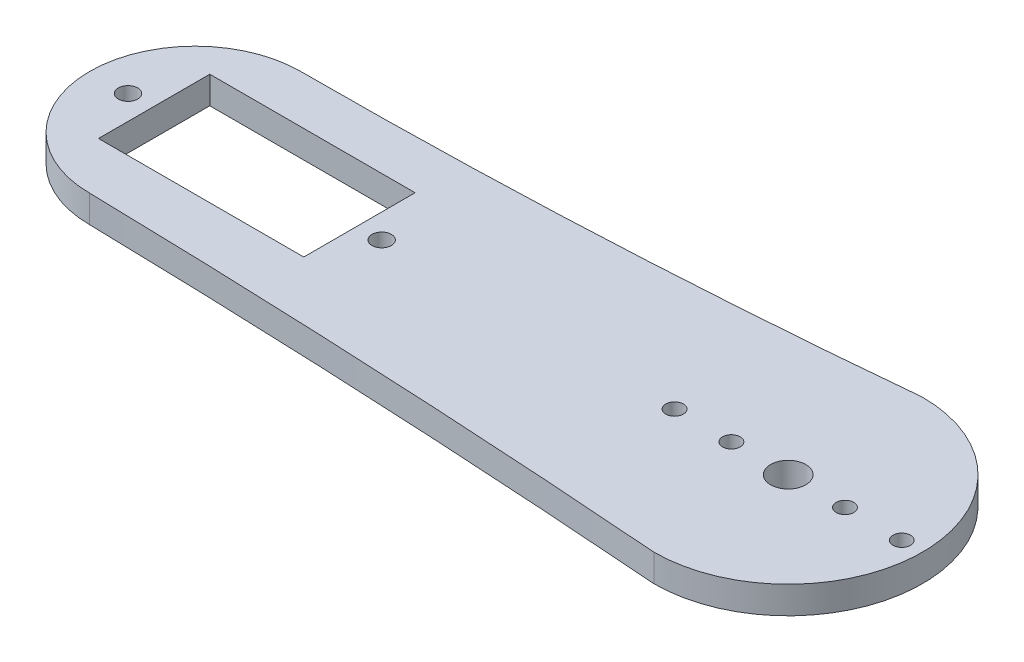
SolidWorks part; units mm, degrees
ref_plane "Front Plane" through (0, 0, 0) normal (0, 0, 1) x (1, 0, 0)
ref_plane "Top Plane" through (0, 0, 0) normal (0, 1, 0) x (1, 0, 0)
ref_plane "Right Plane" through (0, 0, 0) normal (1, 0, 0) x (0, 0, -1)
sketch "Sketch1" plane through (0, 0, 0) normal (0, 1, 0) x (1, 0, 0)
  line L0 (-60.7741, 21.1358) -> (-60.7741, 8.9358)
  line L2 (-60.7741, 21.1358) -> (-38.2741, 21.1358)
  line L3 (-38.2741, 21.1358) -> (-38.2741, 8.9358)
  line L4 (-38.2741, 8.9358) -> (-60.7741, 8.9358)
  arc A0 (-56.0696, 26.3799) -> (-56.0696, 3.2662) centre (-56.0696, 14.823) ccw
  arc A1 (8.9304, 0.1083) -> (8.9304, 29.5377) centre (8.9304, 14.823) ccw
  arc A2 (8.9304, 0.1083) -> (-56.0696, 3.2662) centre (-80.9604, -1179.6232) ccw
  circle A4 centre (-56.0696, 14.823) radius 2.1715
  circle A5 centre (8.9304, 14.823) radius 1.9302
  circle A6 centre (-63.4241, 14.823) radius 1.0616
  circle A7 centre (-35.6241, 14.823) radius 1.0616
  circle A8 centre (2.7054, 14.823) radius 0.9651
  circle A9 centre (-3.5196, 14.823) radius 0.9651
  circle A10 centre (15.1554, 14.823) radius 0.9651
  circle A11 centre (21.3804, 14.823) radius 0.9651
  arc A12 (-56.0696, 26.3799) -> (8.9304, 29.5377) centre (-56.0696, 696.9266) ccw
  point P0 (-60.7741, 15.0358)
  point P25 (-67.6264, 14.823)
  dimension "D7" = 65
  dimension "D8" = 4.2023
  dimension "D5" = 2.65
  dimension "D6" = 2.65
extrude "Boss-Extrude1" add sketch "Sketch1" along normal blind 3 contours A0 A1 A11 A10 A9 A8 A7 A6 A5 L3 L4 L2 region at (-16.1438, 0, -14.6933)
